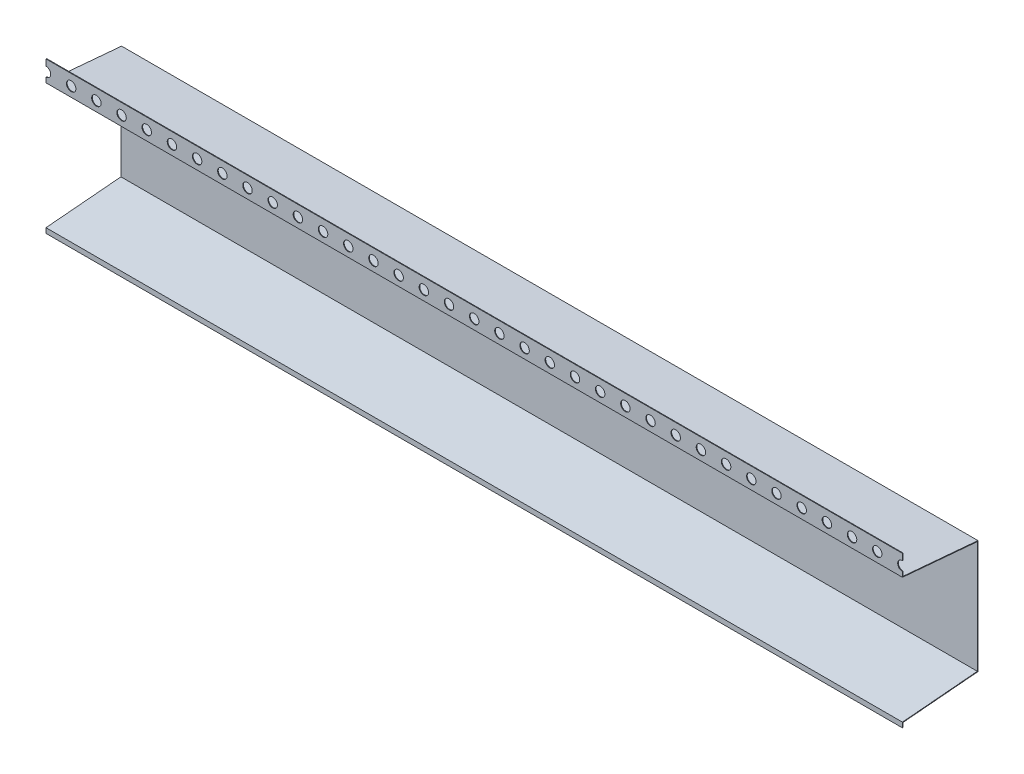
SolidWorks part; units mm, degrees
ref_plane "Top" through (0, 0, 0) normal (0, 0, 1) x (1, 0, 0)
ref_plane "Front" through (0, 0, 0) normal (0, 1, 0) x (1, 0, 0)
ref_plane "Right" through (0, 0, 0) normal (1, 0, 0) x (0, 0, -1)
sketch "Top Sketch" plane through (0, 0, 0) normal (0, 0, 1) x (1, 0, 0)
  line L1 (-136, 0) -> (0, 0)
  line L2 (-136, 0) -> (-136, -24)
  line L3 (-136, -24) -> (0, -24)
  line L4 (0, 0) -> (0, -24)
  dimension "Length" = 136
  dimension "Width" = 24
extrude "Thickness Extrude" add sketch "Top Sketch" against normal blind 0.1
sketch "Pin Hole Sketch" plane through (0, 0, 0) normal (0, 0, 1) x (1, 0, 0)
  line L0 (0, 0) -> (-136, 0) construction
  line L2 (0, -24) -> (0, 0) construction
  circle A0 centre (0, -1.75) radius 0.75
  dimension "D1" = 1.5
  dimension "D2" = 1.75
extrude "First Pin Hole Cut" cut sketch "Pin Hole Sketch" against normal through all
pattern_linear "Pin Hole Pattern" count 35 spacing 4 along (-1, 0, 0) of "First Pin Hole Cut"
sketch "Pocket Sketch" plane through (0, 0, 0) normal (1, 0, 0) x (0, 0, -1)
  line L0 (0, -3.2916) -> (11.9, -4.3327)
  line L1 (0, -24) -> (0, -2.5) construction
  line L2 (11.9, -4.3327) -> (11.9, -22.1673)
  line L3 (11.9, -22.1673) -> (0, -23.2084)
  line L4 (0.1, -3.2) -> (12, -4.2411)
  line L5 (0.1, -24) -> (0.1, -2.5) construction
  line L6 (12, -4.2411) -> (12, -22.2589)
  line L7 (12, -22.2589) -> (0.1, -23.3)
  line L8 (11.9, -13.25) -> (0, -13.25) construction
  line L9 (0.1, -3.2) -> (0, -3.2916)
  line L10 (0, -23.2084) -> (0.1, -23.3)
  dimension "Edge to Pocket Center" = 13.25
  dimension "D2" = 0.1
  dimension "D3" = 0.1
  dimension "D4" = 0.1
  dimension "D5" = 95
  dimension "Pocket Width" = 20.1
  dimension "D6" = 95
  dimension "Pocket Depth" = 12
sketch "Pocket Cut Out Sketch" plane through (0, 0, 0) normal (1, 0, 0) x (0, 0, -1)
  line L0 (0, -3.2916) -> (0, -23.2084)
  line L1 (0, -23.2084) -> (11.9, -22.1673)
  line L2 (11.9, -22.1673) -> (11.9, -4.3327)
  line L3 (11.9, -4.3327) -> (0, -3.2916)
extrude "Pocket Cut Out" cut sketch "Pocket Cut Out Sketch" against normal through all
extrude "Pocket" add sketch "Pocket Sketch" against normal through all
